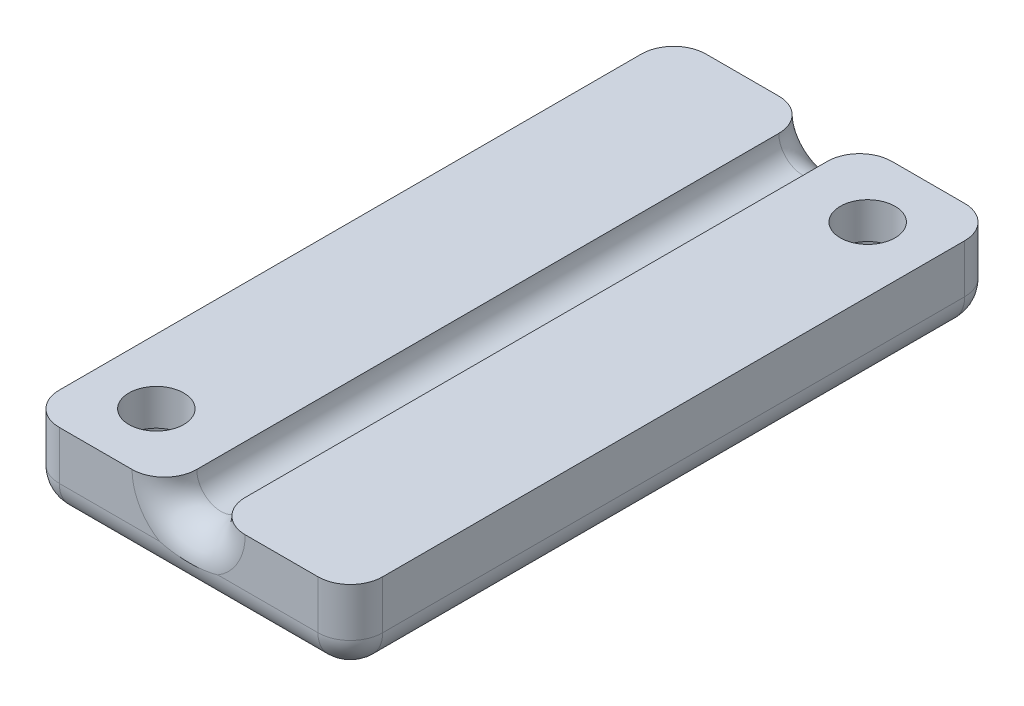
SolidWorks part; units mm, degrees
ref_plane "Front Plane" through (0, 0, 0) normal (0, 0, 1) x (1, 0, 0)
ref_plane "Top Plane" through (0, 0, 0) normal (0, 1, 0) x (1, 0, 0)
ref_plane "Right Plane" through (0, 0, 0) normal (1, 0, 0) x (0, 0, -1)
sketch "Sketch2" plane through (0, 0, 0) normal (0, 0, 1) x (1, 0, 0)
  line L1 (0, 0) -> (25.4, 0)
  line L2 (0, 0) -> (0, 6.35)
  line L3 (0, 6.35) -> (25.4, 6.35)
  line L4 (25.4, 0) -> (25.4, 6.35)
  dimension "D1" = 25.4
  dimension "D2" = 6.35
extrude "Boss-Extrude1" add sketch "Sketch2" along normal blind 50.8
sketch "Sketch3" plane through (0, 0, 50.8) normal (0, 0, 1) x (1, 0, 0)
  line L0 (25.4, 6.35) -> (0, 6.35) construction
  circle A0 centre (12.7, 6.35) radius 1.905
  dimension "D1" = 3.81
extrude "Cut-Extrude1" cut sketch "Sketch3" against normal through all
hole_wizard "CBORE for #6 Socket Head Cap Screw1" positions "Sketch4" profile "Sketch5" counterbore size "#6" standard "ANSI Inch" end condition through all
sketch "Sketch4" plane through (0, 0, 0) normal (0, -1, 0) x (-1, 0, 0)
  line L1 (-25.4, -50.8) -> (-25.4, 0) construction
  line L2 (0, -50.8) -> (0, 0) construction
  line L6 (0, 0) -> (-25.4, 0) construction
  line L7 (0, -50.8) -> (-25.4, -50.8) construction
  point P0 (-20.32, -5.08)
  point P2 (-5.08, -45.72)
  dimension "D1" = 5.08
  dimension "D2" = 5.08
  dimension "D3" = 5.08
  dimension "D4" = 5.08
sketch "Sketch5" plane through (20.32, 0, 5.08) normal (1, 0, 0) x (0, 0, -1)
  line L0 (0, 0) -> (0, 6.35)
  line L1 (0, 6.35) -> (2.1526, 6.35)
  line L3 (2.1526, 6.35) -> (2.1527, 3.5052)
  line L4 (2.1527, 3.5052) -> (3.5725, 3.5052)
  line L5 (3.5725, 3.5052) -> (3.5725, 0)
  line L7 (3.5725, 0) -> (0, 0)
  line L11 (0, -6.35) -> (0, 107.95) construction
  dimension "Thru Hole Dia." = 4.3053
  dimension "Thru Hole Depth" = 6.35
  dimension "C'Bore Dia." = 7.145
  dimension "C'Bore Depth" = 3.5052
fillet "Fillet1" radius 2.54 10 edges at (12.7, 0, 50.8) (0, 0, 25.4) (25.4, 0, 25.4) (12.7, 0, 0) (12.7, 4.445, 50.8) (12.7, 4.445, 0) (0, 3.175, 50.8) (25.4, 3.175, 50.8) (0, 3.175, 0) (25.4, 3.175, 0)
